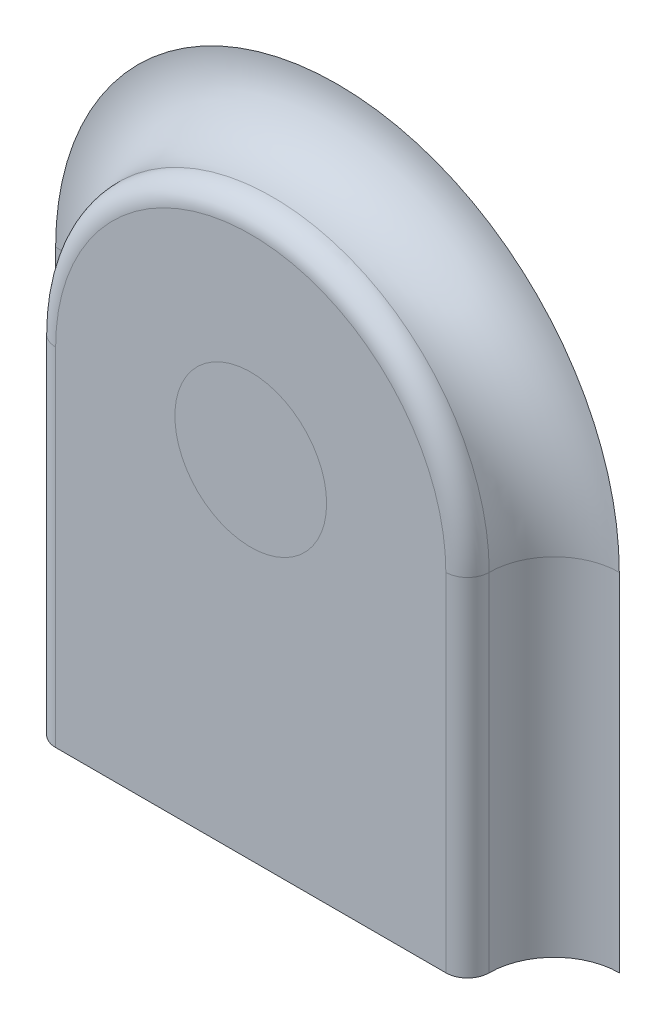
SolidWorks part; units mm, degrees
ref_plane "前视基准面" through (0, 0, 0) normal (0, 0, 1) x (1, 0, 0)
ref_plane "上视基准面" through (0, 0, 0) normal (0, 1, 0) x (1, 0, 0)
ref_plane "右视基准面" through (0, 0, 0) normal (1, 0, 0) x (0, 0, -1)
sketch "草图1" plane through (0, 0, 0) normal (0, 0, 1) x (1, 0, 0)
  line L2 (-5, 0) -> (-5, -8)
  line L3 (-5, -8) -> (5, -8)
  line L4 (5, 0) -> (5, -8)
  arc A0 (5, 0) -> (-5, 0) centre (0, 0) ccw
  dimension "D1" = 10
  dimension "D2" = 8
extrude "凸台-拉伸1" add sketch "草图1" along normal blind 2
sketch "草图2" plane through (0, 0, 0) normal (0, 0, -1) x (-1, 0, 0)
  line L0 (5, -8) -> (-5, -8) construction
  line L1 (-9.5, 7) -> (7.5, 7)
  line L2 (-9.5, 7) -> (-9.5, -10)
  line L3 (-9.5, -10) -> (7.5, -10)
  line L4 (7.5, 7) -> (7.5, -10)
  line L5 (5, 0) -> (5, -8) construction
  dimension "D1" = 17
  dimension "D2" = 2
  dimension "D3" = 2.5
extrude "凸台-拉伸2" add sketch "草图2" along normal blind 5
fillet "圆角1" radius 1.5 3 edges at (5, -4, 0) (0, 5, 0) (-5, -4, 0)
fillet "圆角2" radius 0.5 3 edges at (5, -4, 2) (-5, -4, 2) (0, 5, 2)
sketch "草图3" plane through (-7.5, 0, 0) normal (-1, 0, 0) x (0, 0, 1)
  line L0 (-5, 7) -> (0, 7) construction
  line L1 (-5, 7) -> (0, 7)
  line L2 (-5, -10) -> (-5, 7) construction
  line L3 (-5, -10) -> (-5, 7)
  line L4 (-5, -10) -> (0, -10) construction
  line L5 (-5, -10) -> (0, -10)
  line L6 (0, -10) -> (0, 7) construction
  line L7 (0, -10) -> (0, 7)
extrude "切除-拉伸4" cut sketch "草图3" against normal through all
sketch "草图4" plane through (0, 0, 2) normal (0, 0, 1) x (1, 0, 0)
  circle A0 centre (0, 0) radius 1.75
  dimension "D1" = 3.5
split line "分割线1"
sketch "草图5" plane through (0, 0, 0) normal (0, 0, -1) x (-1, 0, 0)
  line L0 (6.5, -8) -> (6.5, 0) construction
  line L1 (6.5, -8) -> (-6.5, -8) construction
  line L2 (-6.5, 0) -> (-6.5, -8) construction
  line L3 (6.5, -8) -> (6.5, 0)
  line L4 (6.5, -8) -> (-6.5, -8)
  line L5 (-6.5, 0) -> (-6.5, -8)
  line L6 (0, 0) -> (6.5, 0) construction
  line L7 (0, 0) -> (0, 6.5) construction
  arc A0 (6.5, 0) -> (-6.5, 0) centre (0, 0) ccw construction
  arc A1 (6.5, 0) -> (-6.5, 0) centre (0, 0) ccw
